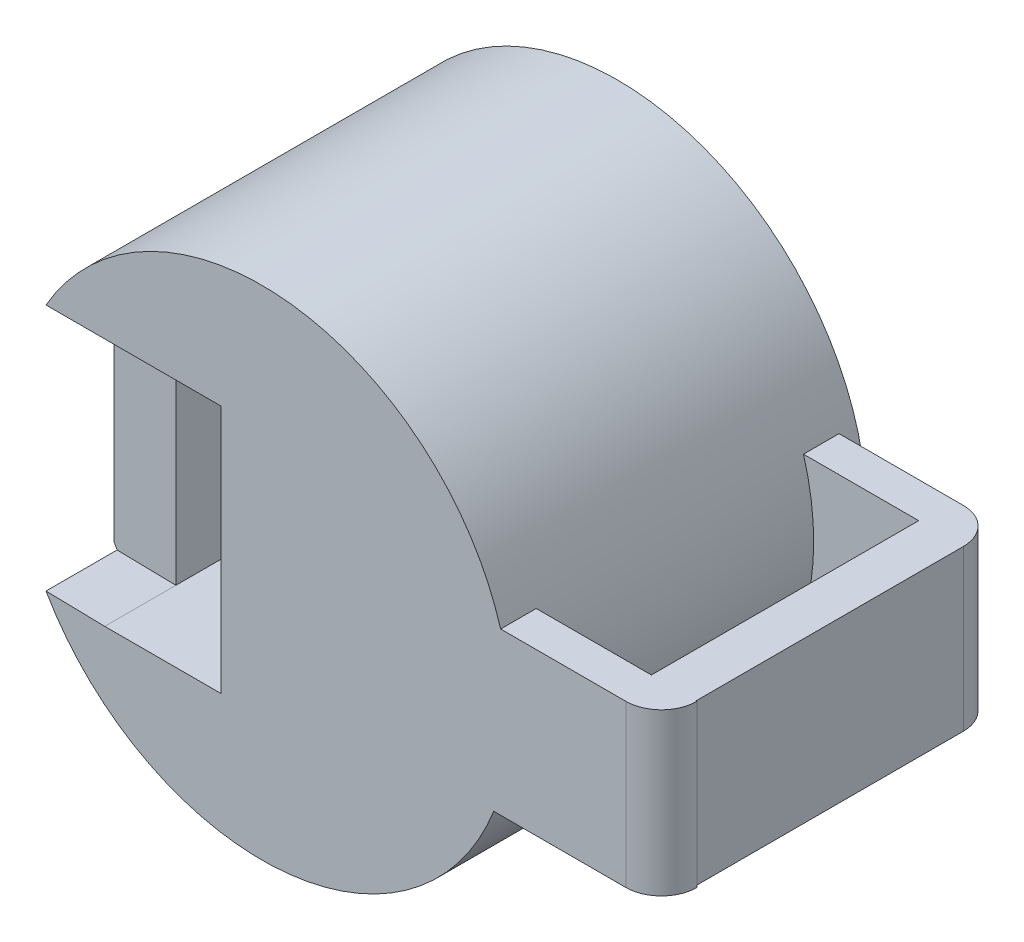
SolidWorks part; units mm, degrees
ref_plane "前基準面" through (0, 0, 0) normal (0, 0, 1) x (1, 0, 0)
ref_plane "上基準面" through (0, 0, 0) normal (0, 1, 0) x (1, 0, 0)
ref_plane "右基準面" through (0, 0, 0) normal (1, 0, 0) x (0, 0, -1)
sketch "草圖1" plane through (0.3827, 0, 0) normal (0, 0, 1) x (1, 0, 0)
  circle A0 centre (-75.5944, 2.55) radius 7
extrude "填料-伸長1" add sketch "草圖1" along normal blind 10 contours A0
ref_plane "平面1" through (0, 0, 9) normal (0, 0, 1) x (1, 0, 0)
sketch "草圖9" plane through (8.1068, 0, 9) normal (0, 0, 1) x (1, 0, 0)
  line L0 (-77.6999, 4.535) -> (-72.0845, 4.535)
  line L1 (-72.0845, 4.535) -> (-72.0845, 0)
  line L2 (-72.0845, 0) -> (-77.6999, 0)
  line L3 (-77.6999, 0) -> (-77.6999, 4.535)
extrude "填料-伸長6" add sketch "草圖9" along normal blind 1
sketch "草圖11" plane through (11.5535, 4.535, 0.4843) normal (0, 1, 0) x (1, 0, 0)
  line L0 (-75.5559, -9) -> (-75.5559, 0)
  line L2 (-75.5559, 0) -> (-76.8136, 0)
  line L3 (-76.8136, 0) -> (-76.8136, -9)
  line L4 (-76.8136, -9) -> (-75.5559, -9)
extrude "填料-伸長7" add sketch "草圖11" against normal blind 4.5 separate body
sketch "草圖12" plane through (-65.2601, 0, 0) normal (-1, 0, 0) x (0, 0, 1)
  line L0 (0.4843, 4.535) -> (0.4843, 0)
  line L1 (0.4843, 4.535) -> (1.4836, 4.535)
  line L2 (1.4836, 4.535) -> (1.4836, 0.035)
  line L3 (0.4843, 0.035) -> (9.4843, 0.035) construction
  line L4 (1.4836, 0.035) -> (0.4843, 0)
extrude "填料-伸長8" add sketch "草圖12" along normal blind 6
fillet "圓角8" radius 1 1 edges at (-64.0025, 2.285, 0.4843)
fillet "圓角9" radius 1 1 edges at (-63.9777, 2.2675, 10)
sketch "草圖14" plane through (0, 0, 10) normal (0, 0, 1) x (1, 0, 0)
  line L1 (-79.6323, 6.0326) -> (-76.3656, 6.0326)
  line L2 (-79.6323, 6.0326) -> (-79.6323, -0.9674)
  line L3 (-79.6323, -0.9674) -> (-76.3656, -0.9674)
  line L4 (-76.3656, 6.0326) -> (-76.3656, -0.9674)
extrude "除料-伸長1" cut sketch "草圖14" against normal blind 10 contours L2 L3 L4 L1
sketch "草圖15" plane through (0, 0, 10) normal (0, 0, 1) x (1, 0, 0)
  line L0 (-79.6323, 6.0326) -> (-81.2839, 6.0326)
  line L1 (-81.2839, -0.9326) -> (-79.6323, -0.9674)
  line L2 (-79.6323, -0.9674) -> (-79.6323, 6.0326)
  arc A0 (-68.4991, 4.535) -> (-68.6927, 0) centre (-75.2117, 2.55) ccw construction
  arc A1 (-81.2839, 6.0326) -> (-81.2839, -0.9326) centre (-75.2117, 2.55) ccw
extrude "除料-伸長2" cut sketch "草圖15" against normal blind 2
sketch "草圖16" plane through (0, 0, 0) normal (0, 0, -1) x (-1, 0, 0)
  line L0 (79.6323, 6.0326) -> (81.2839, 6.0326)
  line L1 (81.2839, -0.9326) -> (79.6323, -0.9674)
  line L2 (79.6323, -0.9674) -> (79.6323, 6.0326)
  circle A0 centre (75.2117, 2.55) radius 7 construction
  arc A1 (81.2839, 6.0326) -> (81.2839, -0.9326) centre (75.2117, 2.55) cw
extrude "除料-伸長3" cut sketch "草圖16" against normal blind 2
ref_plane "平面2" through (-83.3656, 0, 0) normal (-1, 0, 0) x (0, 0, 1)
sketch "草圖17" plane through (-83.3656, 0, 0) normal (-1, 0, 0) x (0, 0, 1)
  line L0 (2, 6.0326) -> (8, 6.0326)
  line L1 (8, 6.0326) -> (8, -0.9326)
  line L2 (8, -0.9326) -> (2, -0.9326)
  line L3 (2, -0.9326) -> (2, 6.0326)
extrude "除料-伸長5" cut sketch "草圖17" against normal blind 2
